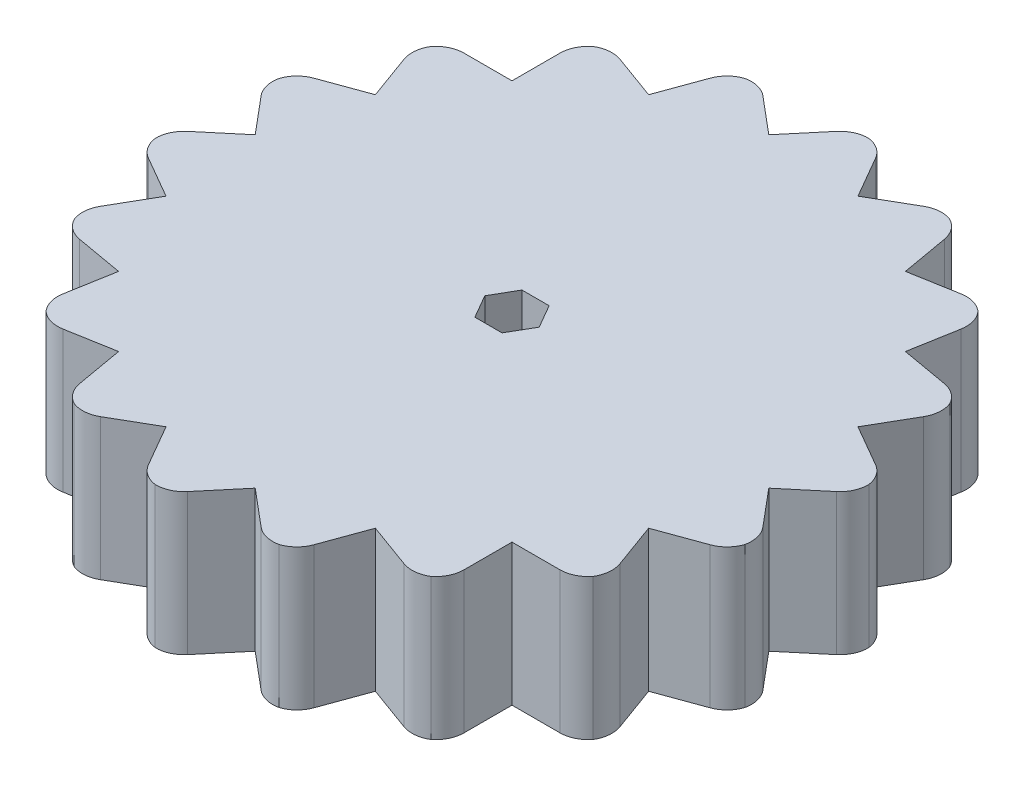
SolidWorks part; units mm, degrees
material "Silicon"
ref_plane "Front Plane" through (0, 0, 0) normal (0, 0, 1) x (1, 0, 0)
ref_plane "Top Plane" through (0, 0, 0) normal (0, 1, 0) x (1, 0, 0)
ref_plane "Right Plane" through (0, 0, 0) normal (1, 0, 0) x (0, 0, -1)
sketch "Sketch1" plane through (0, 0, 0) normal (0, 1, 0) x (1, 0, 0)
  circle A0 centre (0, 0) radius 44.45
  dimension "D1" = 88.9
extrude "Boss-Extrude1" add sketch "Sketch1" along normal blind 19.05 contours A0
sketch "Sketch2" plane through (0, 19.05, 0) normal (0, 1, 0) x (1, 0, 0)
  line L0 (-35.3553, 26.9408) -> (-26.9408, 26.9408)
  line L1 (-35.3553, 26.9408) -> (-35.3553, 35.3553)
  line L2 (-35.3553, 35.3553) -> (-26.9408, 35.3553)
  line L3 (-26.9408, 26.9408) -> (-26.9408, 35.3553)
  circle A0 centre (0, 0) radius 44.45 construction
  dimension "D1" = 26.9408
extrude "Cut-Extrude1" cut sketch "Sketch2" against normal blind 29.972
pattern_circular "CirPattern1" count 18 over 360 about axis through (0, 19.05, 0) along (0, -1, 0) of "Cut-Extrude1"
sketch "Sketch4" plane through (0, 0, 0) normal (0, -1, 0) x (1, 0, 0)
  line L0 (26.9408, 26.9408) -> (26.9408, 35.3553) construction
  line L1 (4.672, -17.4361) -> (14.7866, -10.3537)
  line L2 (14.7866, -10.3537) -> (17.9825, 1.5733)
  line L3 (17.9825, 1.5733) -> (12.7641, 12.7641)
  line L4 (12.7641, 12.7641) -> (1.5733, 17.9825)
  line L5 (1.5733, 17.9825) -> (-10.3537, 14.7866)
  line L6 (-10.3537, 14.7866) -> (-17.4361, 4.672)
  line L7 (-17.4361, 4.672) -> (-16.3599, -7.6287)
  line L8 (-16.3599, -7.6287) -> (-7.6287, -16.3599)
  line L9 (-7.6287, -16.3599) -> (4.672, -17.4361)
  line L10 (0, 0) -> (0, 24.2849) construction
  circle A0 centre (0, 0) radius 16.9625 construction
  dimension "D1" = 33.9251
  dimension "D2" = 8.9583
  dimension "D3" = 65
  dimension "D4" = 18.0511
extrude "Cut-Extrude2" cut sketch "Sketch4" against normal blind 6.35
fillet "Fillet3" radius 3.81 36 edges at (-9.7665, 9.525, -43.3638) (-13.2238, 9.525, -42.4374) (-24.0088, 9.525, -37.4083) (-26.9408, 9.525, -35.3553) (-35.3553, 9.525, -26.9408) (-37.4083, 9.525, -24.0088) (-42.4374, 9.525, -13.2238) (-43.3638, 9.525, -9.7665) (-44.4009, 9.525, 2.0881) (-44.089, 9.525, 5.6537) (-41.009, 9.525, 17.1482) (-39.4964, 9.525, 20.3921) (-32.6709, 9.525, 30.14) (-30.14, 9.525, 32.6709) (-20.3921, 9.525, 39.4964) (-17.1482, 9.525, 41.009) (-5.6537, 9.525, 44.089) (-2.0881, 9.525, 44.4009) (9.7665, 9.525, 43.3638) (13.2238, 9.525, 42.4374) (24.0088, 9.525, 37.4083) (26.9408, 9.525, 35.3553) (35.3553, 9.525, 26.9408) (37.4083, 9.525, 24.0088) (42.4374, 9.525, 13.2238) (43.3638, 9.525, 9.7665) (44.4009, 9.525, -2.0881) (44.089, 9.525, -5.6537) (41.009, 9.525, -17.1482) (39.4964, 9.525, -20.3921) (32.6709, 9.525, -30.14) (30.14, 9.525, -32.6709) (20.3921, 9.525, -39.4964) (17.1482, 9.525, -41.009) (5.6537, 9.525, -44.089) (2.0881, 9.525, -44.4009)
sketch "Sketch6" plane through (0, 19.05, 0) normal (0, 1, 0) x (1, 0, 0)
  line L1 (3.6662, 0) -> (1.8331, 3.175)
  line L2 (1.8331, 3.175) -> (-1.8331, 3.175)
  line L3 (-1.8331, 3.175) -> (-3.6662, 0)
  line L4 (-3.6662, 0) -> (-1.8331, -3.175)
  line L5 (-1.8331, -3.175) -> (1.8331, -3.175)
  line L6 (1.8331, -3.175) -> (3.6662, 0)
  circle A0 centre (0, 0) radius 3.175 construction
  dimension "D1" = 6.35
extrude "Cut-Extrude6" cut sketch "Sketch6" against normal blind 25.908
